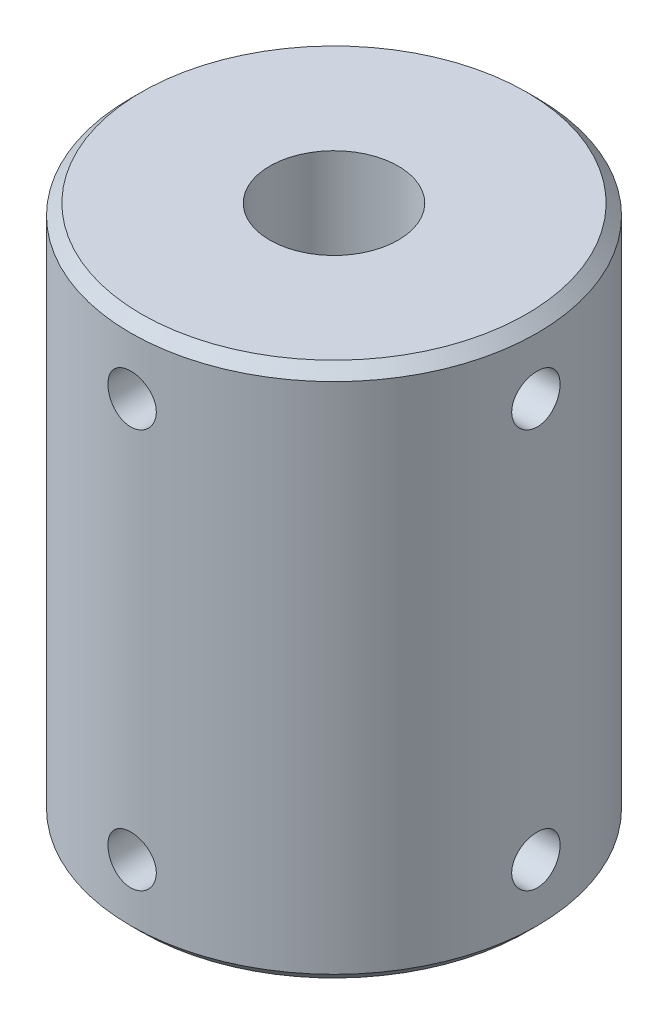
SolidWorks part; units mm, degrees
material "1060 Alloy"
ref_plane "Front" through (0, 0, 0) normal (0, 0, 1) x (1, 0, 0)
ref_plane "Top" through (0, 0, 0) normal (0, 1, 0) x (1, 0, 0)
ref_plane "Right" through (0, 0, 0) normal (1, 0, 0) x (0, 0, -1)
sketch "Sketch1" plane through (0, 0, 0) normal (0, 1, 0) x (1, 0, 0)
  circle A0 centre (0, 0) radius 9.5
  dimension "D1" = 19
extrude "Boss-Extrude1" add sketch "Sketch1" along normal blind 25
chamfer "Chamfer1" distance 0.508 angle 45 2 edges at (0, 0, 9.5) (0, 25, 9.5)
sketch "Sketch2" plane through (0, 25, 0) normal (0, 1, 0) x (1, 0, 0)
  circle A0 centre (0, 0) radius 3
  dimension "D1" = 6
hole_wizard "Ø6.0mm Dowel Hole1" positions "Sketch3" profile "Sketch4" hole size "Ø6.0" standard "ANSI Metric" end condition through all
sketch "Sketch3" plane through (0, 25, 0) normal (0, 1, 0) x (1, 0, 0)
  point P0 (0, 0)
sketch "Sketch4" plane through (0, 25, 0) normal (1, 0, 0) x (0, 0, 1)
  line L0 (0, 0) -> (0, 25)
  line L1 (0, 25) -> (3, 25)
  line L2 (3, 25) -> (3, 0)
  line L5 (3, 0) -> (0, 0)
  line L11 (0, -6.35) -> (0, 107.95) construction
  dimension "Thru Hole Dia." = 6
  dimension "Thru Hole Depth" = 25
sketch "Sketch5" plane through (0, 0, 0) normal (1, 0, 0) x (0, 0, -1)
  line L0 (0, 0) -> (0, 25) construction
  line L1 (3, 25) -> (-3, 25) construction
  circle A0 centre (0, 21.825) radius 1.5
  circle A1 centre (0, 3.175) radius 1.5
  dimension "D2" = 3
  dimension "D1" = 3.175
  dimension "D3" = 3.175
hole_wizard "#4-40 Tapped Hole1" positions "Sketch6" profile "Sketch7" tap size "#4-40" standard "ANSI Inch" end condition through all
sketch "Sketch6" plane through (0, 0, 0) normal (1, 0, 0) x (0, 0, -1)
  point P0 (0, 21.825)
  point P3 (0, 3.175)
sketch "Sketch7" plane through (0, 21.825, 0) normal (0, 1, 0) x (0, 0, 1)
  line L0 (0, 0) -> (0, 9.5)
  line L1 (0, 9.5) -> (1.1303, 9.5)
  line L2 (1.1303, 9.5) -> (1.1303, 0)
  line L5 (1.1303, 0) -> (0, 0)
  line L11 (0, -6.35) -> (0, 107.95) construction
  dimension "Thru Tap Drill Dia." = 2.2606
  dimension "Thru Tap Drill Depth" = 9.5
cosmetic thread "Hole Thread1" parameters "D2"=2.8448
cosmetic thread "Hole Thread2" parameters "D2"=2.8448
sketch "Sketch8" plane through (0, 0, 0) normal (0, 0, 1) x (1, 0, 0)
  line L0 (0, 1.675) -> (0, 4.675) construction
  line L1 (0, 20.325) -> (0, 23.325) construction
  circle A0 centre (0, 3.175) radius 1.5
  circle A1 centre (0, 21.825) radius 1.5
  dimension "D1" = 3
hole_wizard "#4-40 Tapped Hole2" positions "Sketch9" profile "Sketch10" tap size "#4-40" standard "ANSI Inch" end condition through all
sketch "Sketch9" plane through (0, 0, 0) normal (0, 0, 1) x (1, 0, 0)
  point P0 (0, 21.825)
  point P3 (0, 3.175)
sketch "Sketch10" plane through (0, 21.825, 0) normal (1, 0, 0) x (0, 1, 0)
  line L0 (0, 0) -> (0, 9.5)
  line L1 (0, 9.5) -> (1.1303, 9.5)
  line L2 (1.1303, 9.5) -> (1.1303, 0)
  line L5 (1.1303, 0) -> (0, 0)
  line L11 (0, -6.35) -> (0, 107.95) construction
  dimension "Thru Tap Drill Dia." = 2.2606
  dimension "Thru Tap Drill Depth" = 9.5
cosmetic thread "Hole Thread3" parameters "D2"=2.8448
cosmetic thread "Hole Thread4" parameters "D2"=2.8448
sketch "Sketch11" plane through (0, 0, 0) normal (0, 0, 1) x (1, 0, 0)
  line L0 (-9.5, 24.492) -> (-9.5, 0.508) construction
  line L1 (-9.5, 18.65) -> (-3.15, 18.65)
  line L2 (-9.5, 18.65) -> (-9.5, 17.761)
  line L3 (-9.5, 17.761) -> (-3.15, 17.761)
  line L4 (-3.15, 18.65) -> (-3.15, 17.761)
  line L6 (8.992, 25) -> (-8.992, 25) construction
  dimension "D1" = 0.889
  dimension "D2" = 6.35
  dimension "D3" = 6.35
equation "\"D3@Sketch5\"=\"D1@Sketch5\""
